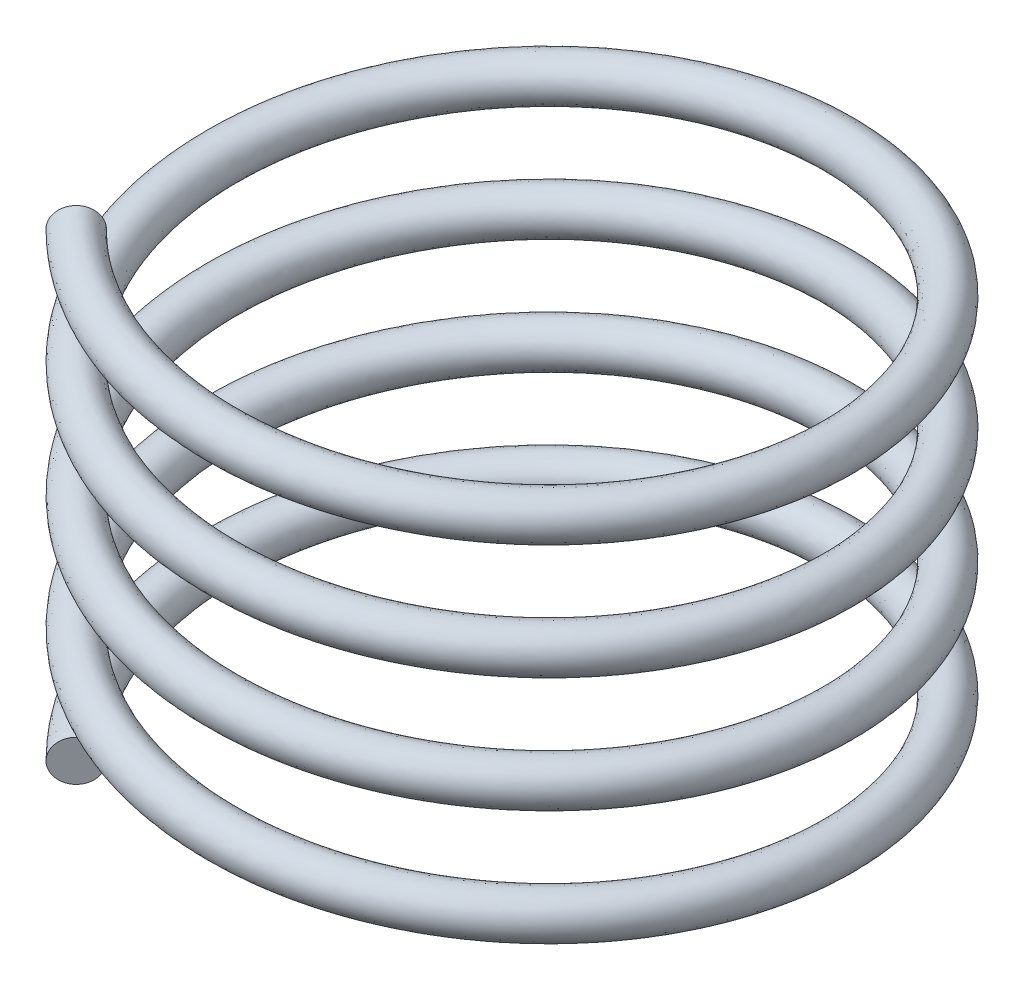
SolidWorks part; units mm, degrees
note: The reader was unsure of these and kept them because the rebuilt part matched: shared geometry of "Sketch1<2>".
ref_plane "Front Plane" through (0, 0, 0) normal (0, 0, 1) x (1, 0, 0)
ref_plane "Top Plane" through (0, 0, 0) normal (0, 1, 0) x (1, 0, 0)
ref_plane "Right Plane" through (0, 0, 0) normal (1, 0, 0) x (0, 0, -1)
sketch "Sketch1" plane through (0, 0, 0) normal (0, 1, 0) x (1, 0, 0)
  circle A0 centre (0, 0) radius 4.675
  dimension "D1" = 9.35
curve "Helix/Spiral1" pitch 1.75 height 7 turns 4 parameters "length"=7
ref_plane "Plane2" through (-3.3057, 0, 3.3057) normal (-0.7059, 0.0595, -0.7059) x (-0.6992, 0.1009, 0.7077)
sketch "Sketch4" plane through (-3.3057, 0, 3.3057) normal (-0.7059, 0.0595, -0.7059) x (-0.6992, 0.1009, 0.7077)
  circle A0 centre (0.0093, 0.0036) radius 0.325
  dimension "D1" = 0.65
sweep "Sweep1" add profiles "Sketch4" path "Helix/Spiral1"
surface "Surface-Extrude2" sketch "Sketch1<2>"
sketch "Sketch1<2>" plane through (0, 0, 0) normal (0, 1, 0) x (1, 0, 0) same geometry as "Sketch1"
